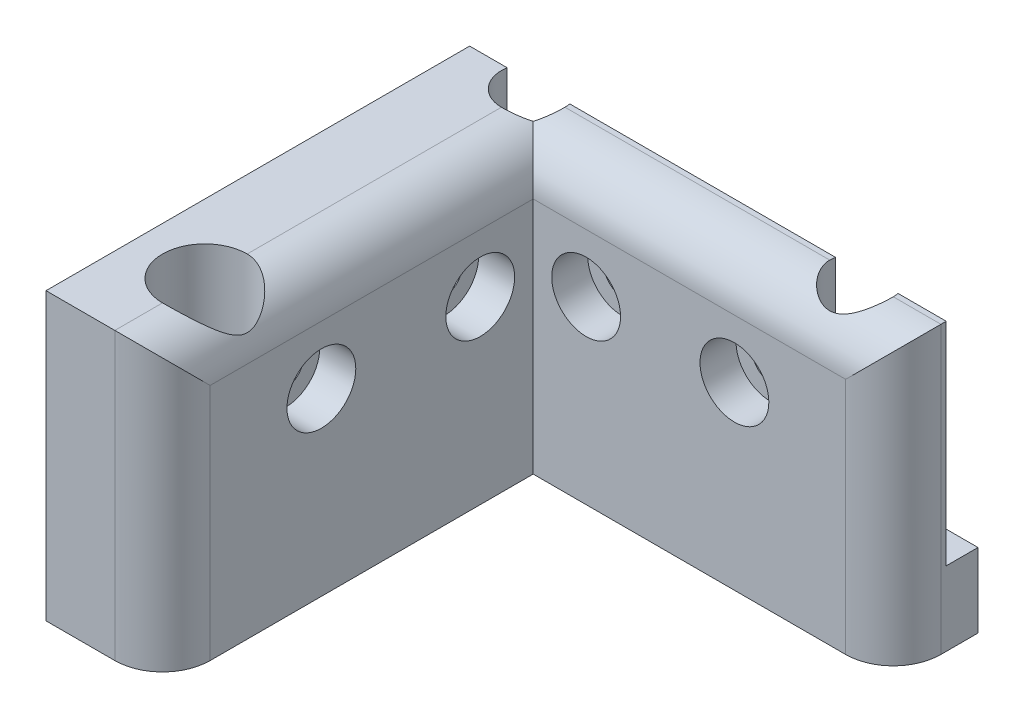
SolidWorks part; units mm, degrees
material "ABS"
ref_plane "Front Plane" through (0, 0, 0) normal (0, 0, 1) x (1, 0, 0)
ref_plane "Top Plane" through (0, 0, 0) normal (0, 1, 0) x (1, 0, 0)
ref_plane "Right Plane" through (0, 0, 0) normal (1, 0, 0) x (0, 0, -1)
sketch "Sketch1" plane through (0, 0, 0) normal (0, 1, 0) x (1, 0, 0)
  line L1 (0, 0) -> (45, 0)
  line L2 (0, 0) -> (0, 40)
  line L3 (0, 40) -> (45, 40)
  line L4 (45, 0) -> (45, 40)
  dimension "D1" = 45
  dimension "D2" = 40
extrude "Boss-Extrude1" add sketch "Sketch1" along normal blind 29
sketch "Sketch33" plane through (0, 29, 0) normal (0, 1, 0) x (1, 0, 0)
  line L0 (0, 40) -> (0, 0) construction
  line L1 (45, 0) -> (11, 0)
  line L2 (45, 0) -> (45, 35)
  line L3 (45, 35) -> (11, 35)
  line L4 (11, 0) -> (11, 35)
  line L5 (45, 40) -> (0, 40) construction
  dimension "D1" = 11
  dimension "D2" = 5
extrude "Cut-Extrude7" cut sketch "Sketch33" against normal through all
sketch "Sketch39" plane through (0, 0, -40) normal (0, 0, -1) x (-1, 0, 0)
  line L0 (0, 29) -> (0, 0) construction
  line L1 (-45, 0) -> (0, 0)
  line L2 (-45, 0) -> (-45, 9)
  line L3 (-45, 9) -> (0, 9)
  line L4 (0, 0) -> (0, 9)
  dimension "D1" = 9
extrude "Boss-Extrude2" add sketch "Sketch39" along normal blind 3
sketch "Sketch21" plane through (0, 29, 0) normal (0, 1, 0) x (1, 0, 0)
  line L0 (45, 40) -> (0, 40) construction
  circle A1 centre (6.5, 39.5) radius 1.75
  circle A2 centre (6.5, 8.5) radius 1.75
  circle A3 centre (37.5, 39.5) radius 1.75
  dimension "D3" = 0.5
  dimension "D4" = 3.5
  dimension "D7" = 3.5
  dimension "D8" = 3.5
  dimension "D1" = 0.5
  dimension "D2" = 31
extrude "Cut-Extrude6" cut sketch "Sketch21" against normal through all both and the other way through all
sketch "Sketch34" plane through (0, 29, 0) normal (0, 1, 0) x (1, 0, 0)
  circle A0 centre (6.5, 8.5) radius 4
  circle A1 centre (6.5, 39.5) radius 3
  circle A2 centre (37.5, 39.5) radius 3
  dimension "D1" = 8
  dimension "D2" = 6
  dimension "D3" = 6
extrude "Cut-Extrude8" cut sketch "Sketch34" against normal blind 23
hole_wizard "CBORE for M3 Hex Socket Head Cap Screw1" positions "Sketch35" profile "Sketch36" counterbore size "M3" standard "ISO" end condition through all
sketch "Sketch35" plane through (11, 0, 0) normal (1, 0, 0) x (0, 0, -1)
  line L1 (0, 0) -> (0, 29) construction
  line L2 (35, 0) -> (35, 29) construction
  line L3 (35, 29) -> (0, 29) construction
  point P0 (15, 19)
  point P2 (30, 19)
  dimension "D1" = 10
  dimension "D2" = 10
  dimension "D3" = 15
  dimension "D4" = 5
sketch "Sketch36" plane through (11, 19, -15) normal (0, 1, 0) x (0, 0, -1)
  line L0 (0, 0) -> (0, 11)
  line L1 (0, 11) -> (1.7, 11)
  line L3 (1.7, 11) -> (1.7, 3.4)
  line L4 (1.7, 3.4) -> (3.25, 3.4)
  line L5 (3.25, 3.4) -> (3.25, 0)
  line L7 (3.25, 0) -> (0, 0)
  line L11 (0, -6.35) -> (0, 107.95) construction
  dimension "Thru Hole Dia." = 3.4
  dimension "Thru Hole Depth" = 11
  dimension "C'Bore Dia." = 6.5
  dimension "C'Bore Depth" = 3.4
hole_wizard "CBORE for M3 Hex Socket Head Cap Screw2" positions "Sketch37" profile "Sketch38" counterbore size "M3" standard "ISO" end condition through all
sketch "Sketch37" plane through (0, 0, -35) normal (0, 0, 1) x (1, 0, 0)
  line L1 (11, 0) -> (11, 29) construction
  line L2 (45, 0) -> (45, 29) construction
  line L3 (45, 29) -> (11, 29) construction
  point P0 (16, 19)
  point P2 (30, 19)
  dimension "D1" = 10
  dimension "D2" = 10
  dimension "D3" = 5
  dimension "D4" = 15
sketch "Sketch38" plane through (16, 19, -35) normal (1, 0, 0) x (0, -1, 0)
  line L0 (0, 0) -> (0, 8)
  line L1 (0, 8) -> (1.7, 8)
  line L3 (1.7, 8) -> (1.7, 3.4)
  line L4 (1.7, 3.4) -> (3.25, 3.4)
  line L5 (3.25, 3.4) -> (3.25, 0)
  line L7 (3.25, 0) -> (0, 0)
  line L11 (0, -6.35) -> (0, 107.95) construction
  dimension "Thru Hole Dia." = 3.4
  dimension "Thru Hole Depth" = 8
  dimension "C'Bore Dia." = 6.5
  dimension "C'Bore Depth" = 3.4
fillet "Fillet1" radius 4.5 4 edges at (11, 14.5, 0) (45, 14.5, -35) (28, 29, -35) (11, 29, -17.5)
sketch "Sketch40" plane through (0, 0, 0) normal (-1, 0, 0) x (0, 0, 1)
  line L0 (-43, 0) -> (-43, 9) construction
  line L1 (-43, 2) -> (0, 2)
  line L2 (-43, 2) -> (-43, 0)
  line L3 (-43, 0) -> (0, 0)
  line L4 (0, 2) -> (0, 0)
  dimension "D1" = 2
extrude "Cut-Extrude9" cut sketch "Sketch40" against normal through all
sketch "Sketch41" plane through (0, 29, 0) normal (0, 1, 0) x (1, 0, 0)
  line L0 (3.542, 40) -> (0, 40) construction
  line L1 (0, 0) -> (6, 0)
  line L2 (0, 0) -> (0, 40)
  line L3 (0, 40) -> (6, 40)
  line L4 (6, 0) -> (6, 40)
  dimension "D1" = 6
extrude "Cut-Extrude10" [suppressed] cut sketch "Sketch41" against normal blind 20
mirror "Mirror1" [suppressed] of bodies 125 122
delete or keep bodies "Body-Delete/Keep 1" [suppressed] type delete bodies bodies 125
